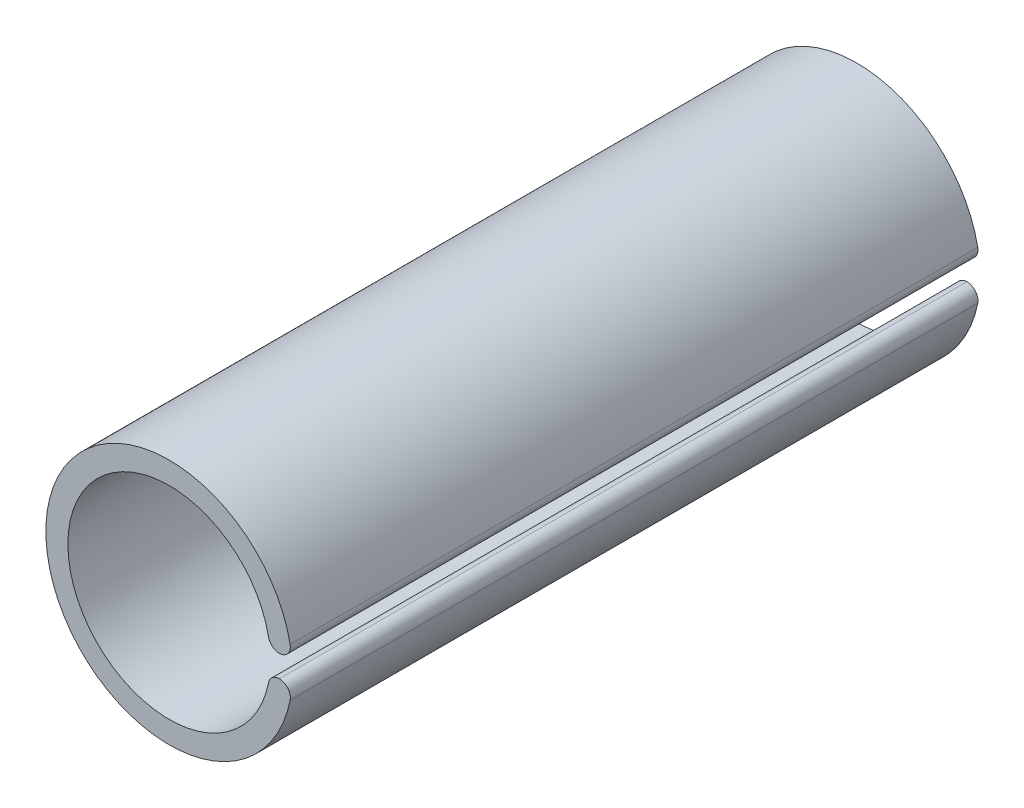
SolidWorks part; units mm, degrees
ref_plane "정면" through (0, 0, 0) normal (0, 0, 1) x (1, 0, 0)
ref_plane "윗면" through (0, 0, 0) normal (0, 1, 0) x (1, 0, 0)
ref_plane "우측면" through (0, 0, 0) normal (1, 0, 0) x (0, 0, -1)
sketch "스케치1" plane through (0, 0, 0) normal (0, 0, 1) x (1, 0, 0)
  circle A0 centre (0, 0) radius 4.6
  circle A1 centre (0, 0) radius 5.6
  dimension "D1" = 9.2
  dimension "D2" = 1
extrude "보스-돌출1" add sketch "스케치1" along normal blind 31.22
sketch "스케치2" plane through (0, 0, 0) normal (0, 0, 1) x (1, 0, 0)
  line L1 (3.1261, 0.5) -> (7.2125, 0.5)
  line L2 (3.1261, 0.5) -> (3.1261, -0.5)
  line L3 (3.1261, -0.5) -> (7.2125, -0.5)
  line L4 (7.2125, 0.5) -> (7.2125, -0.5)
  point P4 (3.1261, 0)
  dimension "D1" = 1
extrude "컷-돌출1" cut sketch "스케치2" along normal through all
fillet "필렛1" radius 0.5 4 edges at (4.5727, -0.5, 15.61) (5.5776, -0.5, 15.61) (5.5776, 0.5, 15.61) (4.5727, 0.5, 15.61)
